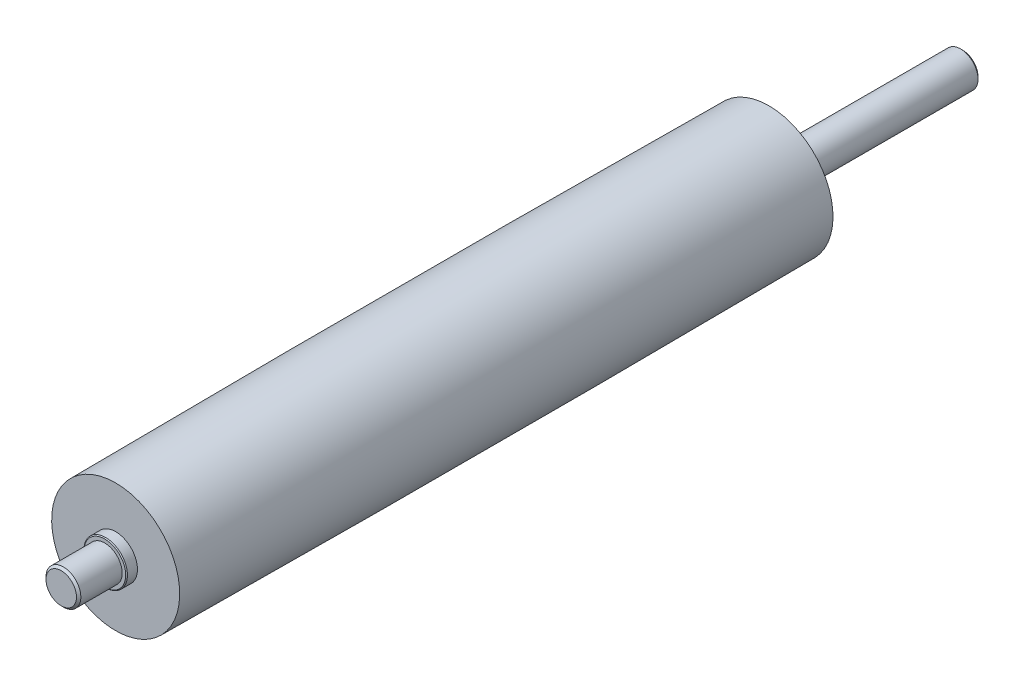
SolidWorks part; units mm, degrees
ref_plane "Front Plane" through (0, 0, 0) normal (0, 0, 1) x (1, 0, 0)
ref_plane "Top Plane" through (0, 0, 0) normal (0, 1, 0) x (1, 0, 0)
ref_plane "Right Plane" through (0, 0, 0) normal (1, 0, 0) x (0, 0, -1)
ref_axis "Axis1" through (0, 0, 75.5781) along (0, 0, -1)
sketch "Sketch1" plane through (0, 0, 0) normal (1, 0, 0) x (0, 0, -1)
  line L0 (77.5, 6) -> (77.5, 4)
  line L1 (77.5, 6) -> (75, 6)
  line L2 (75, 6) -> (75, 14.7)
  line L3 (-75, 14.7) -> (-75, 5)
  line L4 (-75, 5) -> (-77.5, 5)
  line L5 (-33, 0) -> (61.8, 0) construction
  line L6 (87.5, 15) -> (87.5, 0) construction
  line L7 (-33, 4) -> (61.8, 4) construction
  line L8 (119.5, 0) -> (-87.5, 0)
  line L9 (-87.5, 4) -> (-87.5, 0)
  line L18 (0, 0) -> (0, 15) construction
  line L19 (-87.5, 0) -> (-87.5, 15) construction
  line L20 (126.5, 0) -> (126.5, 15) construction
  line L21 (-75, 0) -> (-75, 14.7) construction
  line L22 (75, 0) -> (75, 14.7) construction
  line L56 (119.5, 0) -> (119.5, 4)
  line L59 (119.5, 4) -> (77.5, 4)
  line L65 (-87.5, 0) -> (126.5, 0) construction
  line L66 (-77.5, 5) -> (-77.5, 4)
  line L68 (-87.5, 4) -> (-77.5, 4)
  arc A0 (75, 14.7) -> (-75, 14.7) centre (0, -9360.15) ccw
  point P2 (0, 0)
  point P74 (-45, -6)
  point P75 (61.8, -6)
  point P76 (-45, 6)
  point P77 (61.8, 6)
  point P80 (-45, -3)
  point P81 (61.8, -3)
  dimension "B" = 150
  dimension "FIX_1" = 12.5
  dimension "FIX_2" = 30
  dimension "FIX_3" = 2.5
  dimension "FIX_4" = 10
  dimension "FIX_5" = 8
  dimension "FIX_7" = 42
  dimension "FIX_8" = 12.5
  dimension "FIX_9" = 39
  dimension "FIX_10" = 12
  dimension "FIX_6" = 8
  dimension "FIX_11" = 0.3
revolve "Revolve1" add sketch "Sketch1" angle 360 about L8
chamfer "Chamfer1" distance 0.5 angle 45 2 edges at (0, 4, -119.5) (0, 4, 87.5)
chamfer "Chamfer2" distance 0.2 angle 45 1 edges at (0, 5, 77.5)
sketch "Sketch2" [suppressed] plane through (0, 0, 0) normal (1, 0, 0) x (0, 0, -1)
  line L0 (-15, 0) -> (-15, 14.7) construction
  line L1 (-27.5, 5) -> (-15, 5)
  line L2 (-27.5, 5) -> (-27.5, -5)
  line L3 (-27.5, -5) -> (-15, -5)
  line L4 (-15, 5) -> (-15, -5)
  line L7 (-27.5, 0) -> (-27.5, 15) construction
  line L8 (-15, 5) -> (-17.5, 5) construction
  line L9 (-27.5, 0) -> (59.5, 0) construction
  line L10 (59.5, 0) -> (-27.5, 0) construction
  line L11 (59.5, 0) -> (59.5, 4) construction
  line L12 (15, 6) -> (59.5, 6)
  line L13 (15, 6) -> (15, -6)
  line L14 (15, -6) -> (59.5, -6)
  line L15 (59.5, 6) -> (59.5, -6)
  line L18 (17.5, 6) -> (15, 6) construction
  line L19 (15, 6) -> (15, 14.7) construction
extrude "Cut-Extrude1" [suppressed] cut sketch "Sketch2" against normal through all and the other way through all
sketch "Sketch3" [suppressed] plane through (0, 0, 0) normal (1, 0, 0) x (0, 0, -1)
  line L0 (-59.5, 0) -> (27.5, 0) construction
  line L1 (-51.5, 0) -> (91.5, 0) construction
  line L2 (-17.5, 4) -> (-17.5, 6)
  line L3 (17.5, 4) -> (27.5, 4)
  line L4 (27.5, 4) -> (27.5, 0)
  line L5 (27.5, 0) -> (15, 0)
  line L6 (15, 0) -> (15, 5)
  line L7 (15, 6) -> (15, -6) construction
  line L9 (-59.5, 0) -> (-15, 0)
  line L10 (-59.5, 0) -> (-59.5, 4)
  line L11 (-59.5, 4) -> (-17.5, 4)
  line L12 (-17.5, 6) -> (-15, 6)
  line L13 (-15, 14.7) -> (-15, 5) construction
  line L14 (-15, 6) -> (-15, 0)
  line L15 (15, 5) -> (17.5, 5)
  line L16 (15, 6) -> (15, 14.7) construction
  line L17 (17.5, 5) -> (17.5, 4)
  line L18 (0, 15) -> (0, 0) construction
  line L19 (-15, 5) -> (-17.5, 5) construction
  line L20 (17.5, 6) -> (15, 6) construction
  line L21 (27.5, 15) -> (27.5, 0) construction
  line L22 (59.5, 0) -> (59.5, 4) construction
  line L23 (-27.5, 4) -> (-17.5, 4) construction
  line L24 (59.5, 4) -> (17.5, 4) construction
revolve "Revolve2" [suppressed] add sketch "Sketch3" angle 360 about L0
chamfer "Chamfer3" [suppressed] distance 0.5 angle 45
chamfer "Chamfer4" [suppressed] distance 0.2 angle 45
ref_plane "DISTANCE BETWEEN PULLEYS" through (1000, 0, 0) normal (1, 0, 0) x (0, 0, -1)
ref_plane "CENTERS BETWEEN PULLEYS" through (500, 0, 0) normal (1, 0, 0) x (0, 0, -1)
ref_plane "FRAME TOP" through (0, 14, 0) normal (0, 1, 0) x (1, 0, 0)
ref_plane "FRAME BOTTOM" through (0, -14, 0) normal (0, 1, 0) x (1, 0, 0)
ref_plane "FRAME RAIL UPPER" through (0, 7.5, 0) normal (0, 1, 0) x (1, 0, 0)
ref_plane "FRAME RAIL UNDER" through (0, -4, 0) normal (0, 1, 0) x (1, 0, 0)
ref_plane "FRAME END FACE1" through (0, 0, 87.5) normal (0, 0, 1) x (1, 0, 0)
ref_plane "FRAME END FACE2" through (0, 0, -87.5) normal (0, 0, 1) x (1, 0, 0)
ref_plane "BEAMS1 POSITION1" through (60, 0, 0) normal (1, 0, 0) x (0, 0, -1)
ref_plane "BEAMS1 POSITION2" through (861, 0, 0) normal (1, 0, 0) x (0, 0, -1)
ref_plane "BEAMS1 POSITION3" through (460.5, 0, 0) normal (1, 0, 0) x (0, 0, -1)
ref_plane "BEAMS1 POSITION4" through (328.3333, 0, 0) normal (1, 0, 0) x (0, 0, -1)
ref_plane "BEAMS1 POSITION5" through (593.6667, 0, 0) normal (1, 0, 0) x (0, 0, -1)
ref_plane "BEAMS2 POSITION1" through (63, 0, 0) normal (1, 0, 0) x (0, 0, -1)
ref_plane "BEAMS2 POSITION2" through (859, 0, 0) normal (1, 0, 0) x (0, 0, -1)
ref_plane "BEAMS2 POSITION3" through (474.5, 0, 0) normal (1, 0, 0) x (0, 0, -1)
ref_plane "BEAMS2 POSITION4" through (342.3333, 0, 0) normal (1, 0, 0) x (0, 0, -1)
ref_plane "BEAMS2 POSITION5" through (607.6667, 0, 0) normal (1, 0, 0) x (0, 0, -1)
ref_plane "MOTOR POSITION1" through (0, -69.5, 0) normal (0, 1, 0) x (1, 0, 0)
ref_plane "MOTOR POSITION2" through (31.5, 0, 0) normal (1, 0, 0) x (0, 0, -1)
ref_plane "SPEED CONTROLLER POSITION" through (-100, 0, 0) normal (1, 0, 0) x (0, 0, -1)
ref_plane "CAPACITOR POSITION1" through (0, -61.5, 0) normal (0, 1, 0) x (1, 0, 0)
ref_plane "CAPACITOR POSITION2" through (73.5, 0, 0) normal (1, 0, 0) x (0, 0, -1)
ref_plane "INVERTER POSITION" through (-100, 0, 0) normal (1, 0, 0) x (0, 0, -1)
ref_plane "NUT POSITION1" through (100, 0, 0) normal (1, 0, 0) x (0, 0, -1)
ref_plane "NUT POSITION2" through (112, 0, 0) normal (1, 0, 0) x (0, 0, -1)
ref_plane "NUT POSITION3" through (124, 0, 0) normal (1, 0, 0) x (0, 0, -1)
ref_plane "NUT POSITION4" through (136, 0, 0) normal (1, 0, 0) x (0, 0, -1)
ref_plane "FRAME RAIL INSCRIBED L1" through (0, 0, 86.4) normal (0, 0, 1) x (1, 0, 0)
ref_plane "FRAME RAIL INSCRIBED R1" through (0, 0, -86.4) normal (0, 0, 1) x (1, 0, 0)
ref_plane "FRAME RAIL INSCRIBED L2" through (0, 0, 85.5) normal (0, 0, 1) x (1, 0, 0)
ref_plane "FRAME RAIL INSCRIBED R2" through (0, 0, -85.5) normal (0, 0, 1) x (1, 0, 0)
ref_plane "CONVEYOR STAND POSITION" through (200, 0, 0) normal (1, 0, 0) x (0, 0, -1)
ref_axis "ROTATION AXIS OF MOTOR " through (-16.5, -69.5, 0) along (1, 0, 0)
ref_axis "ROTATION AXIS OF CAPACITOR" through (16.5, -61.5, 0) along (-1, 0, 0)
equation "\"KSS_2@BEAMS1 POSITION4\" = 370 + ( \"L@DISTANCE BETWEEN PULLEYS\" - 1305 ) / 3"
equation "\"KSS_5@BEAMS2 POSITION4\" = 381 + ( \"L@DISTANCE BETWEEN PULLEYS\" - 1305 ) / 3"
equation "\"KSS_6@BEAMS2 POSITION5\" = 353 + ( \"L@DISTANCE BETWEEN PULLEYS\" - 1305 ) / 3"
equation "\"KSS_3@BEAMS1 POSITION5\" = 369 + ( \"L@DISTANCE BETWEEN PULLEYS\" - 1305 ) / 3"
equation "\"KSS_1@BEAMS1 POSITION3\" = 453 + ( \"L@DISTANCE BETWEEN PULLEYS\" - 1105 ) / 2"
equation "\"KSS_4@BEAMS2 POSITION3\" = 464 + ( \"L@DISTANCE BETWEEN PULLEYS\" - 1105 ) / 2"
